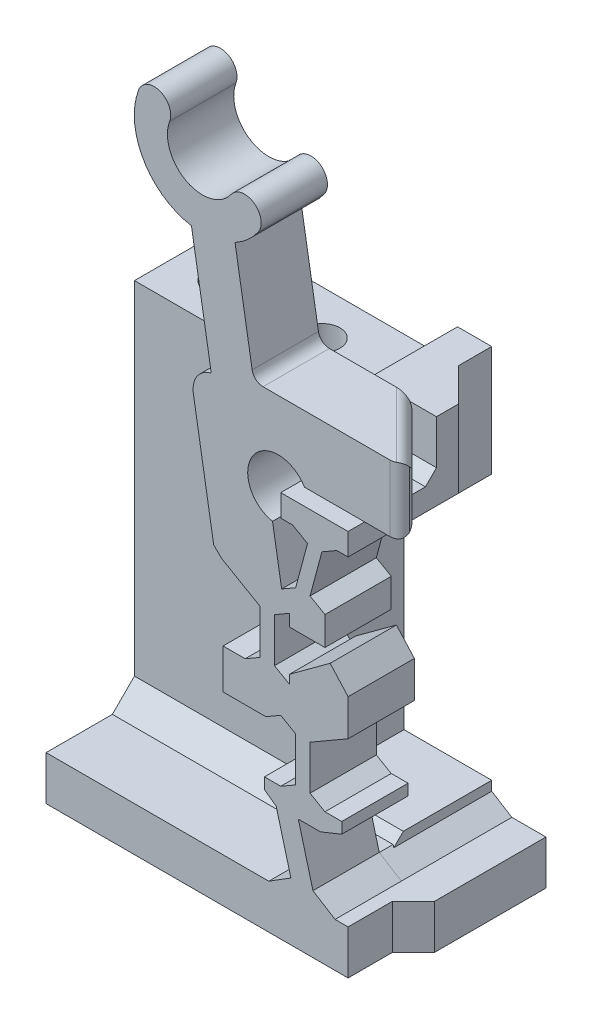
SolidWorks part; units mm, degrees
material "Nylon 6/12"
ref_plane "Front Plane" through (0, 0, 0) normal (0, 0, 1) x (1, 0, 0)
ref_plane "Top Plane" through (0, 0, 0) normal (0, 1, 0) x (1, 0, 0)
ref_plane "Right Plane" through (0, 0, 0) normal (1, 0, 0) x (0, 0, -1)
sketch "Sketch-SkeletonConfigUp" plane through (0, 0, 0) normal (0, 0, 1) x (1, 0, 0)
  line L0 (0, 0) -> (0, -50000) construction
  line L1 (0, 0) -> (4.5811, 6.2164) construction
  line L2 (9.8143, 13.3177) -> (4.5811, 13.945) construction
  line L3 (4.5811, 13.945) -> (2.9713, 10.4094) construction
  line L4 (2.9713, 10.4094) -> (4.5811, 6.2164) construction
  line L5 (4.5811, 13.945) -> (6.2429, 19.1409) construction
  line L6 (2.9713, 10.4094) -> (0.0405, 27.8193) construction
  line L7 (4.5811, 6.2164) -> (9.8143, 13.3177) construction
  line L8 (-587.3593, -797.0242) -> (9.8143, 13.3177) construction
  dimension "D2" = 7.7221
  dimension "D3" = 8.8212
  dimension "D4" = 5.2707
  dimension "D5" = 119.553
  dimension "D6" = 3.8848
  dimension "D7" = 5.4552
  dimension "D8" = 17.6549
  dimension "D9" = 4.4914
  dimension "D10" = 6.745
  dimension "D11" = 145.964
  dimension "D12" = 143.612
sketch "Sketch-SkeletonConfigDown" plane through (0, 0, 0) normal (0, 0, 1) x (1, 0, 0)
  line L0 (0, 0) -> (0, -50000) construction
  line L1 (0, 0) -> (4.5811, 6.2164) construction
  line L2 (9.8143, 13.3177) -> (4.5811, 13.945) construction
  line L3 (4.5811, 13.945) -> (6.1909, 10.4094) construction
  line L4 (6.1909, 10.4094) -> (4.5811, 6.2164) construction
  line L5 (4.5811, 13.945) -> (1.753, 18.6098) construction
  line L6 (6.1909, 10.4094) -> (-8.8652, 19.6294) construction
  line L7 (4.5811, 6.2164) -> (9.8143, 13.3177) construction
  line L8 (-589.9357, -800.5203) -> (9.8143, 13.3177) construction
  dimension "D2" = 7.7221
  dimension "D3" = 8.8212
  dimension "D4" = 5.2707
  dimension "D5" = 119.553
  dimension "D6" = 3.8848
  dimension "D7" = 5.4552
  dimension "D8" = 17.6549
  dimension "D9" = 4.4914
  dimension "D10" = 6.745
  dimension "D11" = 145.964
  dimension "D1" = 143.612
ref_plane "Plane-Cam Base" through (9.128, 0, 0) normal (1, 0, 0) x (0, 0, -1)
ref_plane "Plane-Down-to-Up Derailleur Clearance" through (6.628, 0, 0) normal (1, 0, 0) x (0, 0, -1)
ref_plane "Plane-Cam Cavity Roof" through (5.128, 0, 0) normal (1, 0, 0) x (0, 0, -1)
sketch "Sketch-SwitchBossUp" plane through (0, 0, 0) normal (0, 0, 1) x (1, 0, 0)
  line L0 (3.5811, 11.4759) -> (3.5811, 12.945) construction
  line L5 (5.5811, 12.5552) -> (5.5811, 11.263)
  line L7 (1.5115, 25.1048) -> (2.3566, 20.0847)
  line L8 (-0.4607, 24.7728) -> (0.4359, 19.4465)
  line L9 (2.9713, 10.4094) -> (0.0405, 27.8193) construction
  line L11 (-0.0396, 22.2712) -> (1.9326, 22.6032) construction
  line L15 (6.628, -23.7286) -> (6.628, 23.7286) construction
  line L16 (2.9713, 10.4094) -> (4.5811, 6.2164) construction
  line L17 (3.5811, 12.945) -> (3.5811, 14.945) construction
  line L18 (5.5811, 12.945) -> (5.5811, 14.945) construction
  line L19 (4.2561, 13.945) -> (4.9061, 13.945) construction
  line L20 (3.5811, 14.945) -> (5.5811, 14.945) construction
  line L21 (3.5811, 12.945) -> (5.5811, 12.945) construction
  line L22 (4.5811, 12.945) -> (4.5811, 14.945) construction
  line L23 (4.5811, 6.2164) -> (8.5405, 7.1023) construction
  line L24 (1.9713, 9.4094) -> (1.9713, 11.4094) construction
  line L25 (3.9713, 9.4094) -> (3.9713, 11.4094) construction
  line L26 (3.9713, 9.4094) -> (1.9713, 9.4094) construction
  line L27 (1.9713, 11.4094) -> (3.9713, 11.4094) construction
  line L28 (3.5811, 7.2164) -> (5.5811, 7.2164) construction
  line L29 (3.5811, 7.2164) -> (3.5811, 5.2164) construction
  line L30 (5.5811, 7.2164) -> (5.5811, 5.2164) construction
  line L31 (3.5811, 5.2164) -> (5.5811, 5.2164) construction
  line L32 (4.9061, 6.2164) -> (4.2561, 6.2164) construction
  line L40 (3.2963, 10.4094) -> (2.6463, 10.4094) construction
  line L66 (0.0405, 27.8193) -> (0.0405, 50027.8193) construction
  line L74 (0.5455, 12.7717) -> (-0.3728, 18.2264)
  line L75 (0.3841, 13.7302) -> (2.3564, 14.0622) construction
  line L76 (5.5811, 11.263) -> (5.5811, 12.5552) construction
  line L77 (5.5811, 7.6061) -> (6.628, 8.2105)
  line L80 (5.8152, 10.763) -> (6.628, 9.8603)
  line L81 (9.128, 1033.2419) -> (9.128, 20.0586) construction
  line L82 (4.6532, 17.0847) -> (9.028, 17.0847)
  line L85 (6.9307, 9.5241) -> (8.5405, 7.7363) construction
  line L88 (5.7256, 16.3347) -> (6.628, 16.3347)
  line L92 (3.7762, 8.3129) -> (6.9307, 9.5241) construction
  line L95 (2.3566, 20.0847) -> (7.4359, 20.0847)
  line L96 (7.4359, 20.0847) -> (9.028, 20.0847)
  line L97 (3.2085, 15.0241) -> (3.6203, 12.5779)
  line L98 (1.9713, 9.0197) -> (0.9713, 9.0197)
  line L99 (0.9713, 9.0197) -> (0.9713, 7.2164)
  line L100 (0.9713, 7.2164) -> (2.9061, 7.2164)
  line L101 (4.5811, 6.2164) -> (6.9307, 9.5241) construction
  line L103 (0.0405, 27.8193) -> (1.9448, 26.4638) construction
  line L104 (6.9307, 9.5241) -> (8.5405, 7.7363) construction
  line L107 (1.9713, 9.4094) -> (1.9713, 9.0197) construction
  line L109 (0.0405, 27.8193) -> (-2.1498, 28.6358) construction
  line L111 (6.628, 9.8603) -> (6.628, 8.2105)
  line L112 (6.628, 9.8603) -> (6.9307, 9.5241) construction
  line L113 (2.8424, 4.8267) -> (2.8424, 4.3267)
  line L114 (7.3693, 7.7363) -> (7.3563, 7.7363) construction
  line L121 (5.0383, -1.1653) -> (5.0383, 1.4614) construction
  line L122 (2.8616, 17.0847) -> (3.2085, 15.0241) construction
  line L127 (5.5811, 15.3347) -> (5.5811, 14.945) construction
  line L130 (6.0388, 0.837) -> (6.628, 0.837)
  line L132 (2.8424, 4.3267) -> (3.3749, 3.937)
  line L133 (2.9713, 10.4094) -> (6.1909, 10.4094) construction
  line L134 (4.5811, 10.4094) -> (4.5811, 13.945) construction
  line L135 (4.5811, 10.4094) -> (4.5811, 6.2164) construction
  line L136 (0.8973, 12.4192) -> (0.5455, 12.7717)
  line L137 (3.9713, 9.4094) -> (5.5811, 7.2164) construction
  line L139 (5.8152, 10.763) -> (3.9713, 9.4094)
  line L141 (4.0386, 1.4604) -> (3.0388, 0.8347)
  line L142 (3.0388, 0.8347) -> (3.0388, -1.1653)
  line L143 (9.128, 20.0586) -> (9.128, 18.3333) construction
  line L145 (9.128, 16.6071) -> (9.128, -49992.4167) construction
  line L147 (5.5811, 11.263) -> (5.5811, 12.5552) construction
  line L150 (3.0388, -1.1653) -> (5.0383, -1.1653)
  line L151 (3.3749, 3.937) -> (4.3749, 3.937) construction
  line L152 (4.792, 14.945) -> (4.2561, 12.945)
  line L153 (5.442, 14.945) -> (4.9061, 12.945)
  line L157 (3.5811, 16.3347) -> (3.5811, 15.3347)
  line L158 (6.117, 15.3347) -> (6.628, 15.3347)
  line L162 (3.2963, 11.4094) -> (3.2963, 9.4094)
  line L164 (2.6463, 11.4094) -> (2.6463, 9.4094)
  line L169 (4.2561, 7.2164) -> (4.2561, 5.2164)
  line L170 (4.9061, 5.2164) -> (4.9061, 7.2164)
  line L175 (4.2561, 7.2164) -> (3.5811, 7.6061)
  line L176 (4.9061, 7.2164) -> (5.5811, 7.6061)
  line L177 (5.5811, 7.2164) -> (5.5811, 7.6061) construction
  line L179 (4.2561, 5.2164) -> (3.5811, 4.8267)
  line L180 (3.5811, 5.2164) -> (3.5811, 4.8267) construction
  line L181 (3.5811, 4.8267) -> (2.8424, 4.8267)
  line L183 (4.9061, 5.2164) -> (5.5811, 4.8267)
  line L184 (5.5811, 5.2164) -> (5.5811, 4.8267) construction
  line L186 (9.128, -23.7286) -> (9.128, 23.7286) construction
  line L187 (2.6463, 9.4094) -> (1.9713, 9.0197)
  line L188 (3.2963, 9.4094) -> (3.9713, 9.0197)
  line L189 (3.2963, 11.4094) -> (3.9713, 11.7991)
  line L190 (2.6463, 11.4094) -> (0.8973, 12.4192)
  line L191 (3.9713, 11.4094) -> (3.9713, 11.7991) construction
  line L192 (3.9713, 11.7991) -> (3.9713, 11.263)
  line L193 (4.9061, 12.945) -> (5.5811, 12.5552)
  line L194 (4.2561, 12.945) -> (3.6203, 12.5779)
  line L195 (3.9713, 11.263) -> (5.5811, 11.263)
  line L196 (3.9713, 9.4094) -> (3.9713, 9.0197)
  line L197 (3.5811, 7.2164) -> (3.5811, 7.6061) construction
  line L199 (3.5811, 7.6061) -> (2.9061, 7.2164)
  line L201 (2.8424, 4.3267) -> (2.8424, 3.937) construction
  line L202 (2.8424, 3.937) -> (3.3749, 3.937) construction
  line L204 (5.0383, 1.437) -> (3.0388, 1.437) construction
  line L205 (3.0388, 1.437) -> (3.0388, 0.8347) construction
  line L206 (5.0383, 1.4614) -> (6.0388, 0.837)
  line L207 (9.128, 18.3333) -> (9.128, 16.6071) construction
  line L208 (6.628, -1.1653) -> (6.628, 0.837)
  line L209 (9.128, 20.0586) -> (9.128, 16.6071) construction
  line L211 (5.0383, 1.4614) -> (4.3749, 3.937)
  line L212 (4.0386, 1.4604) -> (3.3749, 3.937)
  line L214 (4.792, 14.945) -> (4.1169, 15.3347)
  line L215 (4.1169, 15.3347) -> (3.5811, 15.3347)
  line L216 (5.442, 14.945) -> (6.117, 15.3347)
  line L217 (5.5811, 12.945) -> (5.5811, 12.5552) construction
  line L218 (5.442, 14.945) -> (5.442, 15.3347) construction
  line L219 (6.117, 15.3347) -> (4.1169, 15.3347) construction
  line L221 (9.028, 17.0847) -> (9.028, 20.0847)
  line L224 (3.5811, 16.3347) -> (5.7256, 16.3347)
  line L232 (6.628, 15.3347) -> (6.628, 16.3347)
  line L233 (6.628, -1.1653) -> (5.0383, -1.1653)
  line L240 (4.3749, 3.937) -> (5.3749, 3.937)
  line L241 (5.3749, 3.937) -> (6.3424, 4.3267)
  line L248 (2.8616, 17.0847) -> (4.6532, 17.0847) construction
  line L367 (5.5811, 4.8267) -> (6.3424, 4.8267)
  line L368 (6.3424, 4.8267) -> (6.3424, 4.3267)
  arc A0 (1.5115, 25.1048) -> (2.5558, 26.0289) centre (0.0405, 27.8193) ccw
  arc A1 (-0.4607, 24.7728) -> (-2.8525, 28.8978) centre (0.0405, 27.8193) cw
  arc A2 (-2.8525, 28.8978) -> (-1.447, 28.3738) centre (-2.1498, 28.6358) cw
  arc A3 (2.5558, 26.0289) -> (1.3338, 26.8987) centre (1.9448, 26.4638) ccw
  arc A4 (-1.447, 28.3738) -> (1.3338, 26.8987) centre (0.0405, 27.8193) ccw
  arc A5 (3.5811, 12.945) -> (3.5811, 14.945) centre (3.1778, 13.945) ccw construction
  arc A6 (5.5811, 12.945) -> (5.5811, 14.945) centre (5.9843, 13.945) cw construction
  arc A7 (2.5293, 9.921) -> (1.9713, 11.4094) centre (1.568, 10.4094) ccw construction
  arc A8 (3.9713, 11.4094) -> (3.9713, 9.4094) centre (4.3745, 10.4094) ccw construction
  arc A9 (3.5811, 7.2164) -> (3.5811, 5.2164) centre (3.1779, 6.2164) cw construction
  arc A10 (5.5811, 7.2164) -> (5.5811, 5.2164) centre (5.9844, 6.2164) ccw construction
  arc A19 (-0.3728, 18.2264) -> (0.4359, 19.4465) centre (0.6836, 18.4042) cw
  circle A28 centre (0.0405, 27.8193) radius 2.3375 construction
  arc A29 (1.9713, 9.4094) -> (2.5293, 9.921) centre (1.568, 10.4094) ccw construction
  arc A37 (3.2085, 15.0241) -> (4.6532, 17.0847) centre (3.4651, 16.381) cw
  point P53 (4.5811, 13.945)
  point P63 (2.9713, 10.4094)
  point P93 (0.9465, 22.4372)
  dimension "D23" = 1.5875
  dimension "D24" = 0.75
  dimension "D2" = 2
  dimension "D5" = 2
  dimension "D6" = 0.65
  dimension "D8" = 42
  dimension "D16" = 42
  dimension "D27" = 120
  dimension "D28" = 120
  dimension "D29" = 120
  dimension "D30" = 120
  dimension "D31" = 120
  dimension "D32" = 120
  dimension "D33" = 120
  dimension "D34" = 120
  dimension "D17" = 0.5
  dimension "D21" = 1
  dimension "D9" = 17.5
  dimension "D22" = 1
  dimension "D38" = 2
  dimension "D39" = 0.5
  dimension "D40" = 60
  dimension "D41" = 1
  dimension "D42" = 45
  dimension "D43" = 120
  dimension "D10" = 15
  dimension "D12" = 2.5
  dimension "D13" = 1
  dimension "D19" = 1
  dimension "D25" = 15
  dimension "D26" = 120
  dimension "D35" = 120
  dimension "D20" = 3
  dimension "D48" = 2
  dimension "D49" = 0.6
  dimension "D7" = 0.75
  dimension "D14" = 3
  dimension "D82" = 1
  dimension "D83" = 3.5
extrude "Boss-Switch Body" add sketch "Sketch-SwitchBossUp" along normal blind 3
sketch "Sketch1" plane through (0, 0, 0) normal (0, 0, -1) x (-1, 0, 0)
  line L1 (-7.5811, -1.1653) -> (0.4122, -1.1653)
  line L2 (-7.5811, -1.1653) -> (-7.5811, 0.837)
  line L4 (0.4122, -1.1653) -> (0.4122, 0.8347)
  line L5 (-3.5811, 18.8347) -> (-7.5811, 18.8347)
  line L10 (-7.5811, 18.8347) -> (-7.5811, 15.3347)
  line L11 (-4.0386, 1.4604) -> (-5.0386, 1.4604)
  line L12 (-7.5811, 15.3347) -> (-3.5811, 15.3347)
  line L13 (-4.0386, 1.4604) -> (-3.0388, 0.8347)
  line L14 (-3.5811, 15.3347) -> (-3.5811, 18.8347)
  line L20 (-4.3749, 3.937) -> (-5.0383, 1.4614) construction
  line L22 (-3.0388, -1.1653) -> (-6.628, -1.1653) construction
  line L23 (-3.0388, 0.8347) -> (0.4122, 0.8347)
  line L24 (-5.0386, 1.4604) -> (-6.0388, 0.837)
  line L25 (-6.0388, 0.837) -> (-7.5811, 0.837)
  dimension "D1" = 3.5
extrude "Boss-Flange Width" add sketch "Sketch1" along normal blind 5
ref_plane "Plane-Sta2Sit Groove" through (0.0405, 0, 0) normal (1, 0, 0) x (0, 0, -1)
ref_plane "Plane-Cam Outer Surface" through (-12.0395, 0, 0) normal (1, 0, 0) x (0, 0, -1)
ref_plane "Plane-FlangeTop" through (-7.0395, 0, 0) normal (1, 0, 0) x (0, 0, -1)
sketch "Sketch2" plane through (-7.0395, 0, 0) normal (1, 0, 0) x (0, 0, -1)
  line L0 (5, 15.3347) -> (-3, 15.3347) construction
  line L1 (5, 17.3347) -> (1, 17.3347)
  line L2 (5, 17.3347) -> (5, 15.3347)
  line L3 (5, 15.3347) -> (1, 15.3347)
  line L4 (1, 17.3347) -> (1, 15.3347)
  line L5 (-3, -1.1653) -> (-3, 0.837) construction
  line L11 (5, 0.8347) -> (-3, 0.8347)
  line L12 (5, 0.8347) -> (5, -1.1653)
  line L13 (5, -1.1653) -> (-3, -1.1653)
  line L14 (-3, 0.8347) -> (-3, -1.1653)
  line L15 (0, 10.4094) -> (0, 27.8193) construction
  line L17 (5, 0.837) -> (5, -1.1653) construction
  line L18 (-3, 0.8347) -> (0, 0.8347) construction
  dimension "D1" = 1
  dimension "D2" = 2
extrude "Boss-Flange Height" add sketch "Sketch2" along normal up to surface (11.6675 mm away)
sketch "Sketch24" plane through (0, 0, 0) normal (0, 0, 1) x (1, 0, 0)
  line L0 (3.5811, 16.3347) -> (7.5811, 16.3347)
  line L1 (7.5811, 17.0847) -> (7.5811, 15.3347) construction
  line L2 (3.5811, 16.3347) -> (3.5811, 18.8347)
  line L3 (3.5811, 18.8347) -> (7.5811, 18.8347)
  line L4 (7.5811, 18.8347) -> (7.5811, 16.3347)
extrude "Cut-Wall Clearance" cut sketch "Sketch24" against normal up to surface (1 mm away) up to face at (-1.7292, 16.3347, -1)
sketch "Sketch10" plane through (0, 15.3347, 0) normal (0, 1, 0) x (1, 0, 0)
  line L0 (9.128, -23.7286) -> (9.128, 23.7286) construction
  line L1 (7.5811, 5) -> (5.128, 5)
  line L2 (7.5811, 5) -> (7.5811, 2)
  line L3 (7.5811, 2) -> (5.128, 2)
  line L5 (4.628, 7) -> (4.628, 1) construction
  line L6 (3.5811, 1) -> (-7.0395, 1) construction
  line L8 (5.128, 5) -> (5.128, 2)
  dimension "D1" = 1
  dimension "D2" = 0.5
  dimension "D3" = 4.5
extrude "Cut-Up-To-Down Derailleur Clearance" cut sketch "Sketch10" along normal up to next
sketch "Sketch17" plane through (0, 15.3347, 0) normal (0, -1, 0) x (1, 0, 0)
  line L0 (5.128, -5) -> (-7.0395, -5)
  line L1 (5.128, -5) -> (-7.0395, -5) construction
  line L2 (-7.0395, -5) -> (-7.0395, -1)
  line L3 (-7.0395, -1) -> (5.128, -1)
  line L4 (5.128, -1) -> (5.128, -5)
  line L5 (-7.0395, -1) -> (-7.0395, -5) construction
extrude "Boss-Flange Support" add sketch "Sketch17" along normal up to surface (14.5 mm away) up to face at (-2.0003, 0.8347, -1)
sketch "Sketch-HolePositions" plane through (0, -1.1653, 0) normal (0, -1, 0) x (1, 0, 0)
  line L0 (-7.0395, -3) -> (7.5811, -3) construction
  line L1 (7.5811, -5) -> (-7.0395, -5) construction
  line L2 (7.5811, -5) -> (7.5811, 0) construction
  line L4 (-7.0395, -22.2167) -> (-7.0395, 22.2167) construction
  point P6 (-5.0395, -3)
  point P7 (-0.5395, -3)
  dimension "D1" = 2
  dimension "D2" = 4.5
  dimension "D3" = 2
sketch "Sketch6" plane through (0, -1.1653, 0) normal (0, -1, 0) x (-1, 0, 0)
  point P0 (5.0395, 3)
  point P3 (0.5395, 3)
hole_wizard "Tap Drill for M2x0.4 Tap1" positions "Sketch6" profile "Sketch5" hole size "M2x0.4" standard "ANSI Metric" end condition through all
sketch "Sketch5" plane through (-5.0395, -1.1653, -3) normal (1, 0, 0) x (0, 0, -1)
  line L0 (0, 0) -> (0, 30.5511)
  line L1 (0, 30.5511) -> (0.8, 30.5511)
  line L2 (0.8, 30.5511) -> (0.8, 0)
  line L5 (0.8, 0) -> (0, 0)
  line L11 (0, -6.35) -> (0, 107.95) construction
  dimension "Thru Hole Dia." = 1.6
  dimension "Thru Hole Depth" = 30.5511
sketch "Sketch9" plane through (0, -1.1653, 0) normal (0, -1, 0) x (1, 0, 0)
  point P0 (-5.0395, -3)
  point P3 (-0.5395, -3)
hole_wizard "M2 Clearance Hole2" positions "Sketch9" profile "Sketch8" hole size "M2" standard "ANSI Metric"
sketch "Sketch8" plane through (-5.0395, -1.1653, -3) normal (1, 0, 0) x (0, 0, -1)
  line L0 (0, 0) -> (0, 15.721)
  line L1 (0, 15.721) -> (1.2, 15)
  line L2 (1.2, 15) -> (1.2, 0)
  line L5 (1.2, 0) -> (0, 0)
  line L10 (0, 15.721) -> (-1.2, 15) construction
  line L11 (0, -6.35) -> (0, 107.95) construction
  dimension "Hole Dia." = 2.4
  dimension "Hole Depth" = 15
  dimension "Drill Angle" = 118
sketch "Sketch-Measurements for Derailleur Ramps" [suppressed] plane through (0, 0, 0) normal (0, 0, 1) x (1, 0, 0)
  line L0 (3.184, 15.1695) -> (2.4687, 19.4188)
  line L1 (2.8264, 17.2941) -> (1.8402, 17.1281)
  line L2 (2.9713, 10.4094) -> (0.0405, 27.8193) construction
  line L3 (1.8402, 17.1281) -> (-1.3081, 15.0016)
  line L4 (6.1909, 10.4094) -> (-8.8652, 19.6294) construction
  line L5 (1.8402, 17.1281) -> (2.6012, 12.6077)
  line L6 (2.6012, 12.6077) -> (-1.3081, 15.0016)
  line L7 (0.2661, 16.0649) -> (0.2661, 17.1281)
  line L8 (0.2661, 17.1281) -> (1.8402, 17.1281)
  line L9 (6.1909, 10.4094) -> (2.9713, 10.4094)
  line L10 (5.386, 8.3129) -> (3.7762, 8.3129)
  line L11 (2.6116, 18.5698) -> (1.5115, 25.1048) construction
  line L12 (6.1909, 10.4094) -> (4.5811, 6.2164) construction
  line L13 (4.5811, 8.3129) -> (4.5811, 8.7912)
  line L14 (4.5811, 6.2164) -> (5.386, 8.3129)
  line L15 (2.9713, 10.4094) -> (4.5811, 6.2164) construction
  line L16 (3.7762, 8.3129) -> (4.5811, 6.2164)
  line L17 (5.386, 8.3129) -> (5.386, 8.7912)
  dimension "D1" = 1.5742
  dimension "D2" = 0.8049
sketch "Sketch12" plane through (0, 20.0847, 0) normal (0, 1, 0) x (1, 0, 0)
  line L0 (6.528, 0) -> (9.028, -2.5)
  line L1 (9.028, -2.5) -> (9.028, 0)
  line L2 (9.028, 0) -> (6.528, 0)
  line L3 (9.028, -3) -> (9.028, 0) construction
  line L6 (9.028, 0) -> (2.3566, 0) construction
  dimension "D1" = 45
extrude "Cut-Up-to-Down Cantilever Slope" cut sketch "Sketch12" against normal up to next
ref_plane "Plane1" through (0, 7.1023, 0) normal (0, 1, 0) x (1, 0, 0)
ref_plane "Plane-Cantilever Cut" [suppressed] through (7.0848, 8.5204, -1.9058) normal (-0.6301, -0.7578, 0.1695) x (-0.7765, 0.6151, -0.1368)
sketch "Sketch14" [suppressed] plane through (7.0848, 8.5204, -1.9058) normal (-0.6301, -0.7578, 0.1695) x (-0.7765, 0.6151, -0.1368)
  line L0 (2.3023, -1.6911) -> (-0.3551, -1.6911)
  line L2 (2.3023, -4.3362) -> (2.3023, -1.6911)
  line L3 (-0.3551, -1.6911) -> (-0.3551, -4.4608)
  line L5 (-0.3551, -4.4608) -> (1.0087, -5.0843)
  line L6 (1.0087, -5.0843) -> (2.3023, -4.3362)
extrude "Cut-Down-to-Up Cantilever Slope" [suppressed] cut sketch "Sketch14" against normal up to next
ref_plane "Plane-Symmetry Plane" through (0, 0, 1.5) normal (0, 0, 1) x (1, 0, 0)
sketch "Sketch-Cable Center Point" plane through (0, 0, 1.5) normal (0, 0, 1) x (1, 0, 0)
  line L0 (0.0405, 27.8193) -> (0.1722, 27.0366)
  line L1 (2.9713, 10.4094) -> (0.0405, 27.8193) construction
  point P0 (0.0405, 27.8193)
  dimension "D1" = 0.7937
chamfer "Chamfer-Flange Support" distance 1.5 angle 45 1 edges at (3.5811, 17.3347, -3)
chamfer "Chamfer-Flange Support 2" distance 1.5 angle 45 2 edges at (5.128, 17.0847, -2) (5.128, 15.3347, -1.5)
chamfer "Chamfer-Flange Support 3" distance 1 angle 45 1 edges at (-2.0003, 0.8347, -1)
chamfer "Chamfer3" distance 0.5 angle 45 3 edges at (3.5811, 15.8347, -1) (5.1045, 15.3347, -1) (5.5811, 16.3347, -1)
chamfer "Chamfer7" [suppressed] distance 1 angle 45
sketch "Sketch23" plane through (0, 0, -1) normal (0, 0, 1) x (1, 0, 0)
  line L0 (5.128, 1.8347) -> (1.1605, 1.8347)
  line L1 (-7.0395, 1.8347) -> (5.128, 1.8347) construction
  line L2 (1.1605, 1.8347) -> (1.1605, 13.8347)
  line L3 (1.1605, 13.8347) -> (5.128, 13.8347)
  line L4 (5.128, 13.8347) -> (5.128, 1.8347)
  line L5 (0.6605, -1.1653) -> (0.6605, 13.8347) construction
  dimension "D1" = 0.5
extrude "Cut-Gap for Printing" cut sketch "Sketch23" against normal through all
sketch "Sketch25" plane through (0, 0, 0) normal (0, 0, 1) x (1, 0, 0)
  line L0 (6.628, 15.3347) -> (7.5811, 15.3347)
  line L1 (7.5811, 15.3347) -> (7.5811, 18.8347)
  line L2 (7.5811, 18.8347) -> (6.628, 18.8347)
  line L3 (6.628, -23.7286) -> (6.628, 23.7286) construction
  line L4 (7.5811, 18.8347) -> (3.5811, 18.8347) construction
  line L5 (6.628, 18.8347) -> (6.628, 15.3347)
extrude "Cut-Derailleur Clearance" cut sketch "Sketch25" against normal through all
chamfer "Chamfer8" distance 1 angle 45 1 edges at (6.628, -0.1641, 0)
fillet "Fillet1" radius 0.5 5 edges at (6.528, 18.5847, 0) (9.028, 18.5847, 3) (7.778, 20.0847, 1.25) (9.028, 18.5847, 2.5) (7.778, 17.0847, 1.25)
fillet "Fillet2" radius 0.5 1 edges at (2.3566, 20.0847, 1.5)
equation "\"axle-diameter\"=2"
equation "\"switch-thickness\"=12"
equation "\"base-width\"=4.0"
equation "\"axle-bushing-radius\"=3"
equation "\"clearance\"= 0.25"
equation "\"arm-width\"=1.5"
equation "\"min-diameter\"=70"
equation "\"alpha\"=143.6120"
equation "\"gamma\"=119.5526"
equation "\"delta\"=145.9637"
equation "\"epsilon\"=6.7452"
equation "\"l_AB\"=8.8212"
equation "\"l_AC\"=4.4914"
equation "\"l_BD\"=5.2707"
equation "\"l_CD\"=3.8848"
equation "\"l_CE\"=17.6549"
equation "\"l_DF\"=5.4552"
equation "\"l_OA\"=7.7221"
equation "\"D2@Sketch-SkeletonConfigUp\" = \"l_OA\""
equation "\"D3@Sketch-SkeletonConfigUp\" = \"l_AB\""
equation "\"D4@Sketch-SkeletonConfigUp\" = \"l_BD\""
equation "\"D5@Sketch-SkeletonConfigUp\" = \"gamma\""
equation "\"D6@Sketch-SkeletonConfigUp\" = \"l_CD\""
equation "\"D7@Sketch-SkeletonConfigUp\" = \"l_DF\""
equation "\"D8@Sketch-SkeletonConfigUp\" = \"l_CE\""
equation "\"D9@Sketch-SkeletonConfigUp\" = \"l_AC\""
equation "\"D_groove\"=3.175"
equation "\"D7@Sketch-SkeletonConfigDown\" = \"l_DF\""
equation "\"D6@Sketch-SkeletonConfigDown\" = \"l_CD\""
equation "\"D2@Sketch-SkeletonConfigDown\" = \"l_OA\""
equation "\"D3@Sketch-SkeletonConfigDown\" = \"l_AB\""
equation "\"D9@Sketch-SkeletonConfigDown\" = \"l_AC\""
equation "\"D8@Sketch-SkeletonConfigDown\" = \"l_CE\""
equation "\"D5@Sketch-SkeletonConfigDown\" = \"gamma\""
equation "\"D4@Sketch-SkeletonConfigDown\" = \"l_BD\""
equation "\"D1@Sketch-SkeletonConfigDown\" = \"alpha\""
equation "\"hinge_length\"=1.5"
equation "\"hinge_depth\"=0.25"
equation "\"D10@Sketch-SkeletonConfigUp\"=\"epsilon\""
equation "\"D11@Sketch-SkeletonConfigUp\"=\"delta\""
equation "\"D12@Sketch-SkeletonConfigUp\"=\"alpha\""
equation "\"D11@Sketch-SkeletonConfigDown\"=\"delta\""
equation "\"D10@Sketch-SkeletonConfigDown\"=\"epsilon\""
equation "\"EE_dx\"=8.9056"
equation "\"EE_dy\"=8.1898"
equation "\"r_groove\"=\"D_groove\"/2"
equation "\"t_wall\"=25.4/16"
equation "\"width_lower\"=\"D_groove\"+\"t_wall\""
equation "\"cable_to_bottom\"=30.6257"
equation "\"switch_EE-up_base_dy\"=24"
equation "\"switch_EE-down_base_dy\"=16"
equation "\"D_axle\"=25.4/8"
equation "\"D_up_to_down\"=16"
equation "\"D_down_to_up\"=25"
equation "\"t_cam_base\"=7.5"
equation "\"D23@Sketch-SwitchBossUp\"=\"D_groove\"/2"
equation "\"D1@Sketch-Cable Center Point\"=\"D_groove\"/4"
